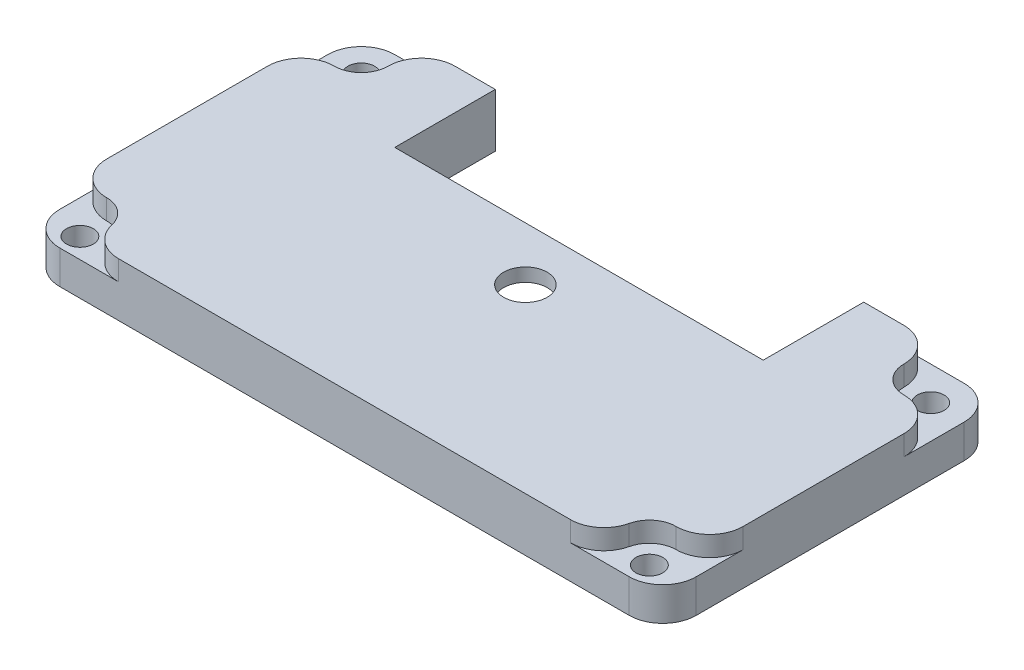
SolidWorks part; units mm, degrees
ref_plane "Front Plane" through (0, 0, 0) normal (0, 0, 1) x (1, 0, 0)
ref_plane "Top Plane" through (0, 0, 0) normal (0, 1, 0) x (1, 0, 0)
ref_plane "Right Plane" through (0, 0, 0) normal (1, 0, 0) x (0, 0, -1)
sketch "Sketch1" plane through (0, 0, 0) normal (0, 1, 0) x (1, 0, 0)
  line L1 (-47.5, -25) -> (47.5, -25)
  line L2 (-47.5, -25) -> (-47.5, 25)
  line L3 (-47.5, 25) -> (47.5, 25)
  line L4 (47.5, -25) -> (47.5, 25)
  line L5 (-47.5, -25) -> (47.5, 25) construction
  line L6 (-47.5, 25) -> (47.5, -25) construction
  point P0 (0, 0)
  dimension "D1" = 50
  dimension "D2" = 95
extrude "Boss-Extrude1" add sketch "Sketch1" along normal blind 8
sketch "Sketch2" plane through (0, 8, 0) normal (0, 1, 0) x (1, 0, 0)
  line L0 (-27.5, 25) -> (-27.5, 10)
  line L2 (47.5, 25) -> (-47.5, 25) construction
  line L3 (-27.5, 10) -> (27.5, 10)
  line L4 (27.5, 10) -> (27.5, 25)
  line L5 (47.5, -25) -> (47.5, 25) construction
  line L6 (-47.5, 25) -> (-47.5, -25) construction
  line L7 (-47.5, -25) -> (47.5, -25) construction
  line L8 (-27.5, 25) -> (27.5, 25)
  dimension "D1" = 20
  dimension "D2" = 20
  dimension "D3" = 35
extrude "Cut-Extrude1" cut sketch "Sketch2" against normal through all
sketch "Sketch3" plane through (0, 8, 0) normal (0, 1, 0) x (1, 0, 0)
  line L0 (0, -25) -> (0, 2) construction
  line L1 (-47.5, -25) -> (47.5, -25) construction
  circle A0 centre (0, 2) radius 3.25
  dimension "D2" = 6.5
  dimension "D1" = 27
extrude "Cut-Extrude2" cut sketch "Sketch3" against normal through all
sketch "Sketch4" plane through (0, 0, 0) normal (0, -1, 0) x (1, 0, 0)
  circle A2 centre (0, -2) radius 10.25
  circle A3 centre (0, -2) radius 10.25
  dimension "D1" = 7
extrude "Cut-Extrude3" cut sketch "Sketch4" against normal blind 6
fillet "Fillet1" radius 5 2 edges at (-6.408, 3, -10) (6.408, 3, -10)
sketch "Sketch5" plane through (0, 8, 0) normal (0, 1, 0) x (1, 0, 0)
  line L0 (47.5, 25) -> (27.5, 25) construction
  line L1 (47.5, -25) -> (47.5, 25) construction
  line L2 (-47.5, -25) -> (47.5, -25) construction
  line L3 (0, -4.4) -> (0, 4.4) construction
  circle A0 centre (42.5, 20) radius 2
  circle A1 centre (42.5, -22) radius 2
  circle A2 centre (-42.5, -22) radius 2
  circle A3 centre (-42.5, 20) radius 2
  dimension "D2" = 5
  dimension "D3" = 4
  dimension "D6" = 4
  dimension "D1" = 5
  dimension "D4" = 3
  dimension "D5" = 5
extrude "Cut-Extrude4" cut sketch "Sketch5" against normal through all
sketch "Sketch6" plane through (0, 8, 0) normal (0, 1, 0) x (1, 0, 0)
  line L0 (-42.5, -18) -> (-47.5, -18)
  line L1 (-47.5, 25) -> (-47.5, -25) construction
  line L2 (-47.5, -18) -> (-47.5, -25)
  line L3 (-47.5, -25) -> (-45.1458, -25)
  line L4 (-47.5, -25) -> (47.5, -25) construction
  line L5 (0, -4.4) -> (0, 4.4) construction
  line L6 (47.5, -25) -> (45.1458, -25)
  line L7 (47.5, -18) -> (47.5, -25)
  line L8 (42.5, -18) -> (47.5, -18)
  line L9 (-42.5, 16) -> (-47.5, 16)
  line L10 (-47.5, 16) -> (-47.5, 25)
  line L11 (-38.5, 20) -> (-38.5, 25)
  line L12 (-27.5, 25) -> (-47.5, 25) construction
  line L13 (-38.5, 25) -> (-47.5, 25)
  line L14 (42.5, 16) -> (47.5, 16)
  line L15 (47.5, -25) -> (47.5, 25) construction
  line L16 (47.5, 16) -> (47.5, 25)
  line L17 (47.5, 25) -> (38.5, 25)
  line L18 (47.5, 25) -> (27.5, 25) construction
  line L19 (38.5, 25) -> (38.5, 20)
  arc A0 (-42.5, -18) -> (-45.1458, -25) centre (-42.5, -22) ccw construction
  arc A1 (45.1458, -25) -> (42.5, -18) centre (42.5, -22) cw
  circle A2 centre (-42.5, -22) radius 4
  arc A3 (-45.1458, -25) -> (-42.5, -18) centre (-42.5, -22) ccw
  arc A4 (42.5, 16) -> (38.5, 20) centre (42.5, 20) cw
  circle A5 centre (-42.5, 20) radius 4
  arc A6 (-42.5, 16) -> (-38.5, 20) centre (-42.5, 20) ccw
  arc A7 (-38.5, 20) -> (-42.5, 16) centre (-42.5, 20) ccw construction
  arc A8 (38.5, 20) -> (42.5, 16) centre (42.5, 20) cw construction
  dimension "D1" = 2
  dimension "D2" = 2
extrude "Cut-Extrude5" cut sketch "Sketch6" against normal blind 3
fillet "Fillet2" radius 5 12 edges at (-47.5, 6.5, 18) (-39.8542, 6.5, 25) (47.5, 6.5, 18) (39.8542, 6.5, 25) (-47.5, 2.5, 25) (47.5, 2.5, 25) (47.5, 2.5, -25) (47.5, 6.5, -16) (38.5, 6.5, -25) (-47.5, 2.5, -25) (-38.5, 6.5, -25) (-47.5, 6.5, -16)
